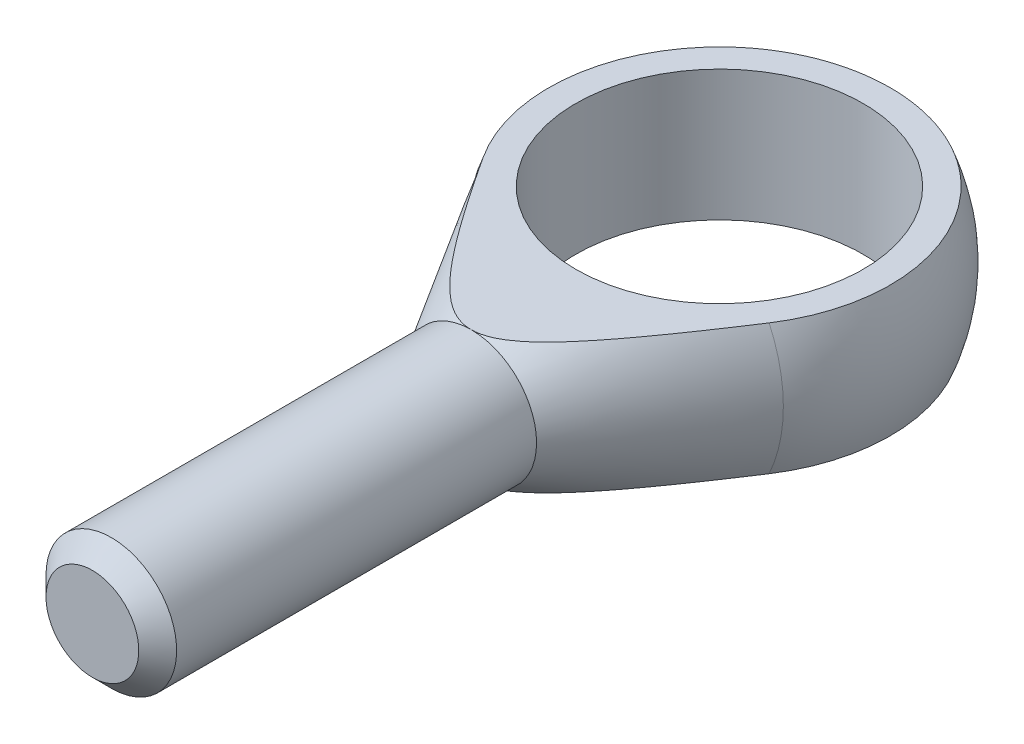
SolidWorks part; units mm, degrees
material "1.0545 (S355N)"
ref_plane "Płaszczyzna przednia" through (0, 0, 0) normal (0, 0, 1) x (1, 0, 0)
ref_plane "Płaszczyzna górna" through (0, 0, 0) normal (0, 1, 0) x (1, 0, 0)
ref_plane "Płaszczyzna prawa" through (0, 0, 0) normal (1, 0, 0) x (0, 0, -1)
sketch "Szkic1" plane through (0, 0, 0) normal (0, 1, 0) x (1, 0, 0)
  line L0 (0, 26.0435) -> (0, -71.4286) construction
  line L1 (-5, -48) -> (5, -48)
  line L2 (5, -48) -> (5, -19)
  line L3 (-5, -48) -> (-5, -19)
  line L4 (-12.0377, -7.148) -> (-5, -19)
  line L5 (5, -19) -> (12.0377, -7.148)
  line L6 (-5, -19) -> (5, -19)
  line L7 (0, 14) -> (0, -48)
  arc A0 (12.0377, -7.148) -> (-12.0377, -7.148) centre (0, 0) ccw
  point P7 (0, -48)
  dimension "d4" = 28
  dimension "d2" = 10
  dimension "l1" = 48
  dimension "l3" = 29
revolve "Obrót1" add sketch "Szkic1" angle 360 about L0 region at (2.5, 0, 33.5) region at (5.7323, 0, 1.8725)
sketch "Szkic2" plane through (0, 0, 0) normal (1, 0, 0) x (0, 0, -1)
  line L4 (-19, 5) -> (13.0767, 5)
  line L5 (-19, -5) -> (13.0767, -5)
  line L6 (-19, -5) -> (-7.148, -12.0377) construction
  line L7 (-7.148, 12.0377) -> (-19, 5) construction
  line L8 (-19, -5) -> (-7.148, -12.0377)
  line L9 (-7.148, 12.0377) -> (-19, 5)
  arc A0 (-7.148, -12.0377) -> (-7.148, 12.0377) centre (0, 0) ccw construction
  arc A1 (-7.148, -12.0377) -> (13.0767, -5) centre (0, 0) ccw
  arc A2 (13.0767, 5) -> (-7.148, 12.0377) centre (0, 0) ccw
extrude "Wytnij-wyciągnięcie1" cut sketch "Szkic2" against normal through all both and the other way through all
sketch "Szkic3" plane through (0, 0, 0) normal (0, 1, 0) x (1, 0, 0)
  circle A0 centre (0, 0) radius 11
  dimension "b" = 22
extrude "Wytnij-wyciągnięcie2" cut sketch "Szkic3" against normal through all both and the other way through all contours A0
chamfer "Sfazowanie1" distance 1.45 angle 45 1 edges at (-5, 0, 48)
equation "\"D1@Sfazowanie1\"=\"l3@Szkic1\"*0.05"
